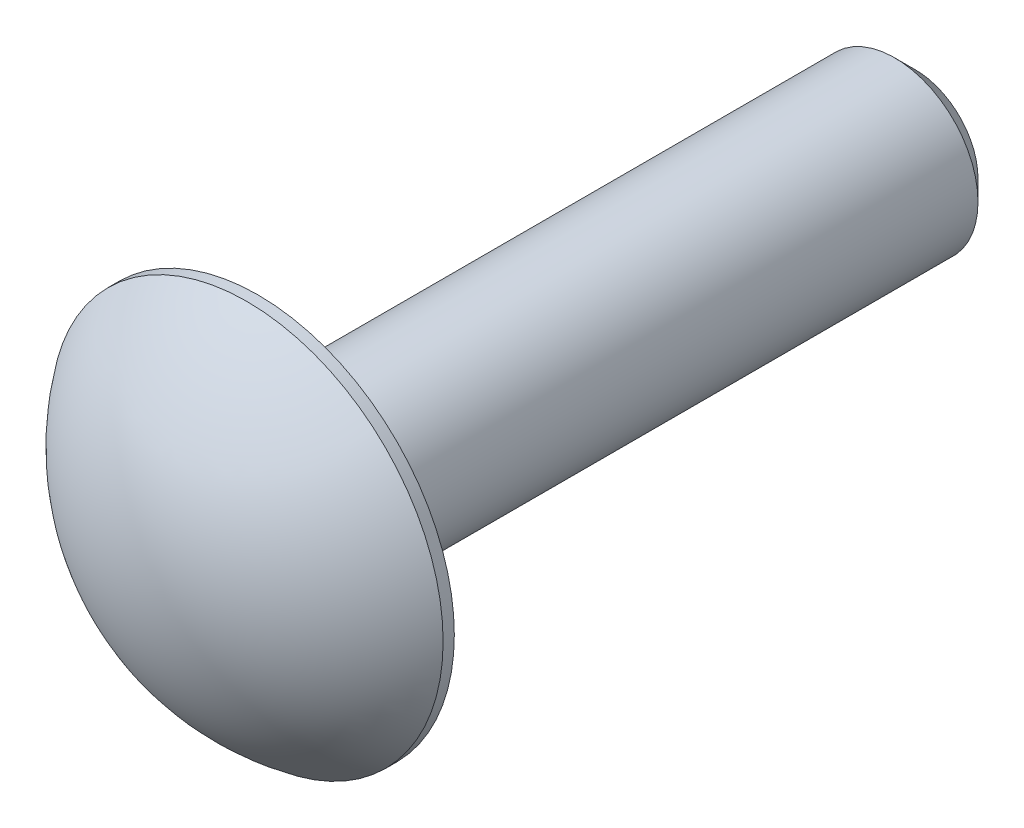
SolidWorks part; units mm, degrees
material "AISI 304"
ref_plane "Front" through (0, 0, 0) normal (0, 0, 1) x (1, 0, 0)
ref_plane "Top" through (0, 0, 0) normal (0, 1, 0) x (1, 0, 0)
ref_plane "Right" through (0, 0, 0) normal (1, 0, 0) x (0, 0, -1)
sketch "Sketch1" plane through (0, 0, 0) normal (0, 0, 1) x (1, 0, 0)
  circle A0 centre (0, 0) radius 5.6896
  dimension "Head Dia" = 11.3792
extrude "Extrude3" add sketch "Sketch1" along normal blind 3.2512
sketch "Sketch11" plane through (0, 0, 0) normal (1, 0, 0) x (0, 0, -1)
  line L0 (0, 0) -> (-3.5052, 0) construction
  line L4 (-3.2512, 5.6896) -> (-3.2512, -5.6896) construction
  line L5 (-3.5052, 6.8275) -> (0, 6.8275)
  line L7 (0, 6.8275) -> (0, 5.6896)
  line L8 (-0.3251, 5.6896) -> (0, 5.6896)
  line L9 (0, -5.6896) -> (0, 5.6896) construction
  line L11 (0, 5.6896) -> (-3.2512, 5.6896) construction
  line L13 (-3.2512, 0) -> (-3.5052, 0)
  line L14 (-3.5052, 0) -> (-3.5052, 6.8275)
  arc A0 (-0.3251, 5.6896) -> (-3.2512, 0) centre (3.7434, 0) ccw
  dimension "D3" = 0.254
  dimension "D1" = 0.3251
  dimension "D5" = 1.1379
revolve "Cut-Revolve3" cut sketch "Sketch11" angle 360 about L0
sketch "Sketch4" plane through (0, 0, 0) normal (1, 0, 0) x (0, 0, -1)
  line L0 (0, 0) -> (19.05, 0)
  line L3 (19.05, 0) -> (19.05, 2.413)
  line L4 (19.05, 2.413) -> (0, 2.413)
  line L6 (0, 2.413) -> (0, 0)
  line L9 (19.05, 2.413) -> (19.05, -2.413) construction
  dimension "length" = 19.05
  dimension "dia" = 4.826
revolve "Revolve1" add sketch "Sketch4" angle 360 about L0
sketch "Sketch13" plane through (0, 0, -19.05) normal (0, 0, -1) x (-1, 0, 0)
  circle A2 centre (0, 0) radius 2.413
curve "Helix/Spiral1" pitch 0.7937 height 22.3012 turns 28.096
chamfer "Chamfer2" distance 0.5953 angle 45 1 edges at (2.413, 0, -19.05)
sketch "Sketch14" plane through (0, 0, 0) normal (1, 0, 0) x (0, 0, -1)
  line L0 (19.05, 2.4378) -> (19.7445, 2.4378)
  line L1 (19.7445, 2.4378) -> (19.4469, 1.9008)
  line L2 (19.4469, 1.9008) -> (19.3477, 1.9008)
  line L3 (19.3477, 1.9008) -> (19.05, 2.4378)
  line L4 (19.1988, 2.1693) -> (19.5957, 2.1693) construction
  dimension "D1" = 0.0992
  dimension "D2" = 58
  dimension "D3" = 0.3969
  dimension "D4" = 0.0248
sweep "Cut-Sweep1" [suppressed] cut profiles "Sketch14" path "Helix/Spiral1"
ref_plane "Plane1" through (0, 0, 19.05) normal (0, 0, -1) x (-1, 0, 0)
sketch "Sketch29" [suppressed] plane through (0, 0, 28.575) normal (0, 0, -1) x (-1, 0, 0)
  circle A0 centre (0, 0) radius 1.7526 construction
  circle A1 centre (0, 0) radius 1.7526
  point P3 (0, -1.7526)
  point P4 (0, 1.7526)
extrude "Extrude11" [suppressed] add sketch "Sketch29" against normal up to surface (28.575 mm away)
ref_plane "Plane2" through (0, 0, 3.2512) normal (0, 0, 1) x (1, 0, 0)
sketch "Sketch26" plane through (0, 0, 0) normal (0, 0, 1) x (1, 0, 0)
  circle A1 centre (0, 0) radius 0.5461
  dimension "D1" = 1.0922
extrude "Extrude13" add sketch "Sketch26" along normal up to surface (3.2298 mm away)
sketch "Sketch31" plane through (0, 0, 3.2512) normal (0, 0, 1) x (1, 0, 0)
  line L0 (-5.6896, 0.6945) -> (5.6896, -0.6945) construction
  line L1 (-5.6896, 0.6945) -> (5.6896, 0.6945)
  line L2 (-5.6896, 0.6945) -> (-5.6896, -0.6945)
  line L3 (-5.6896, -0.6945) -> (5.6896, -0.6945)
  line L4 (5.6896, 0.6945) -> (5.6896, -0.6945)
  circle A0 centre (0, 0) radius 5.6896 construction
  dimension "D1" = 1.3891
extrude "Extrude15" [suppressed] cut sketch "Sketch31" against normal blind 1.6256
sketch "Sketch18" plane through (0, 0, 0) normal (1, 0, 0) x (0, 0, -1)
  line L1 (19.05, 2.413) -> (0, 2.413) construction
  point P0 (17.8594, -2.413)
  point P1 (18.2562, 2.413)
  point P2 (-3.2512, 0.6945)
  dimension "D1" = 0.7937
  dimension "D2" = 1.1906
equation "\"D3@Helix/Spiral1\" = \"length@Sketch4\" + \"Head Ht@Extrude3\""
equation "\"D1@Sketch14\" = \"D4@Helix/Spiral1\" * .125"
equation "\"D3@Sketch14\" = \"D4@Helix/Spiral1\" * .5"
equation "\"D1@Sketch11\" = \"Head Ht@Extrude3\" / 10"
equation "\"D5@Sketch11\" = \"Head Dia@Sketch1\" / 10"
equation "\"D4@Sketch14\" = \"D1@Sketch14\" * .25"
equation "\"D1@Chamfer2\" = \"D4@Helix/Spiral1\" * .75"
equation "\"D1@Sketch18\" = \"D4@Helix/Spiral1\""
equation "\"D2@Sketch18\" = \"D4@Helix/Spiral1\" * 1.5"
equation "\"D1@Extrude15\" = \"Head Ht@Extrude3\" * .5"
equation "\"D1@Sketch31\" = \"D4@Helix/Spiral1\" * 1.75"
